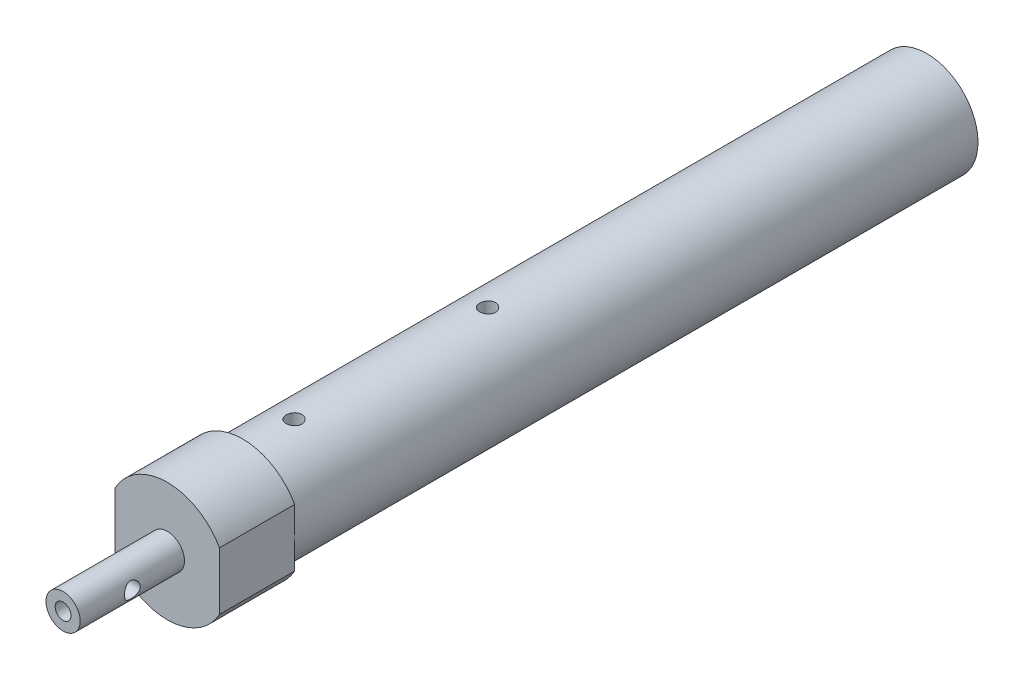
SolidWorks part; units mm, degrees
ref_plane "Front Plane" through (0, 0, 0) normal (0, 0, 1) x (1, 0, 0)
ref_plane "Top Plane" through (0, 0, 0) normal (0, 1, 0) x (1, 0, 0)
ref_plane "Right Plane" through (0, 0, 0) normal (1, 0, 0) x (0, 0, -1)
sketch "Sketch1" plane through (0, 0, 0) normal (0, 0, 1) x (1, 0, 0)
  circle A0 centre (0, 0) radius 8.7312
  dimension "D1" = 17.4625
extrude "Boss-Extrude1" add sketch "Sketch1" along normal blind 129.54
sketch "Sketch2" plane through (0, 0, 129.54) normal (0, 0, 1) x (1, 0, 0)
  circle A0 centre (0, 0) radius 2.921
  dimension "D1" = 5.842
extrude "Boss-Extrude2" add sketch "Sketch2" along normal blind 17.78
ref_plane "Plane1" through (0, 8.7312, 0) normal (0, 1, 0) x (1, 0, 0)
sketch "Sketch4" plane through (0, 8.7312, 0) normal (0, 1, 0) x (1, 0, 0)
  line L1 (-2.921, -147.32) -> (2.921, -147.32) construction
  circle A0 centre (0, -74.93) radius 1.8415
  circle A1 centre (0, -107.95) radius 1.8415
  dimension "D1" = 3.683
  dimension "D2" = 33.02
  dimension "D3" = 39.37
hole_wizard "#6-32 Tapped Hole1" positions "Sketch5" profile "Sketch6" tap size "#6-32" standard "ANSI Inch" end condition through all
sketch "Sketch5" plane through (0, 8.7312, 0) normal (0, 1, 0) x (1, 0, 0)
  point P0 (0, -74.93)
  point P3 (0, -107.95)
sketch "Sketch6" plane through (0, 8.7312, 74.93) normal (1, 0, 0) x (0, 0, 1)
  line L0 (0, 0) -> (0, 17.4625)
  line L1 (0, 17.4625) -> (1.3525, 17.4625)
  line L2 (1.3525, 17.4625) -> (1.3525, 0)
  line L5 (1.3525, 0) -> (0, 0)
  line L11 (0, -6.35) -> (0, 107.95) construction
  dimension "Thru Tap Drill Dia." = 2.7051
  dimension "Thru Tap Drill Depth" = 17.4625
cosmetic thread "Hole Thread1" parameters "D2"=3.5052
cosmetic thread "Hole Thread2" parameters "D2"=3.5052
ref_plane "Plane2" through (2.921, 0, 0) normal (1, 0, 0) x (0, 0, -1)
sketch "Sketch7" plane through (2.921, 0, 0) normal (1, 0, 0) x (0, 0, -1)
  line L1 (-147.32, 2.921) -> (-147.32, -2.921) construction
  circle A0 centre (-138.43, 0) radius 1.8415
  dimension "D1" = 3.683
  dimension "D2" = 8.89
hole_wizard "#6-32 Tapped Hole2" positions "Sketch8" profile "Sketch9" tap size "#6-32" standard "ANSI Inch" end condition through all
sketch "Sketch8" plane through (2.921, 0, 0) normal (1, 0, 0) x (0, 0, -1)
  point P0 (-138.43, 0)
sketch "Sketch9" plane through (2.921, 0, 138.43) normal (0, 1, 0) x (0, 0, -1)
  line L0 (0, 0) -> (0, 11.6522)
  line L1 (0, 11.6522) -> (1.3525, 11.6522)
  line L2 (1.3525, 11.6522) -> (1.3525, 0)
  line L5 (1.3525, 0) -> (0, 0)
  line L11 (0, -6.35) -> (0, 107.95) construction
  dimension "Thru Tap Drill Dia." = 2.7051
  dimension "Thru Tap Drill Depth" = 11.6522
cosmetic thread "Hole Thread3" parameters "D2"=3.5052
sketch "Sketch10" plane through (0, 0, 129.54) normal (0, 0, 1) x (1, 0, 0)
  line L0 (8.89, -4.9187) -> (8.89, 4.9187)
  line L1 (-8.89, -4.9187) -> (-8.89, 4.9187)
  arc A0 (-8.89, -4.9187) -> (8.89, -4.9187) centre (0, 0) ccw
  arc A1 (-8.89, 4.9187) -> (-8.89, -4.9187) centre (0, 0) ccw construction
  arc A2 (8.89, -4.9187) -> (8.89, 4.9187) centre (0, 0) ccw construction
  arc A3 (8.89, 4.9187) -> (-8.89, 4.9187) centre (0, 0) ccw
  point P1 (0, 0)
  point P4 (0, 0)
  point P8 (0, 0)
  dimension "D1" = 20.32
  dimension "D2" = 8.89
  dimension "D3" = 8.89
extrude "Boss-Extrude3" add sketch "Sketch10" against normal blind 12.827
sketch "Sketch11" plane through (0, 0, 147.32) normal (0, 0, 1) x (1, 0, 0)
  point P0 (0, 0)
  point P3 (0, 0)
hole_wizard "#6-32 Tapped Hole3" positions "Sketch12" profile "Sketch13" tap size "#6-32" standard "ANSI Inch"
sketch "Sketch12" plane through (0, 0, 147.32) normal (0, 0, 1) x (1, 0, 0)
  point P0 (0, 0)
sketch "Sketch13" plane through (0, 0, 147.32) normal (1, 0, 0) x (0, -1, 0)
  line L0 (0, 0) -> (0, 7.1627)
  line L1 (0, 7.1627) -> (1.3525, 6.35)
  line L2 (1.3525, 6.35) -> (1.3525, 0)
  line L5 (1.3525, 0) -> (0, 0)
  line L10 (0, 7.1627) -> (-1.3526, 6.35) construction
  line L11 (0, -6.35) -> (0, 107.95) construction
  dimension "Tap Drill Dia." = 2.7051
  dimension "Tap Drill Depth" = 6.35
  dimension "Drill Angle" = 118
